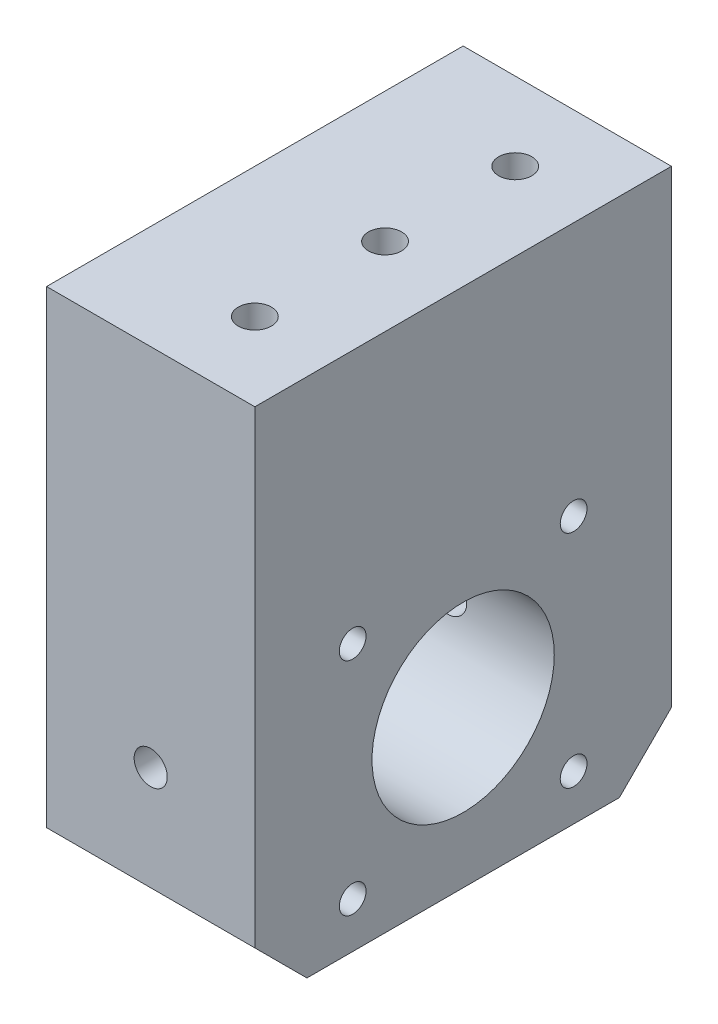
SolidWorks part; units mm, degrees
material "Nylon 6/10"
ref_plane "Front Plane" through (0, 0, 0) normal (0, 0, 1) x (1, 0, 0)
ref_plane "Top Plane" through (0, 0, 0) normal (0, 1, 0) x (1, 0, 0)
ref_plane "Right Plane" through (0, 0, 0) normal (1, 0, 0) x (0, 0, -1)
sketch "Sketch1" plane through (0, 0, 0) normal (1, 0, 0) x (0, 0, -1)
  line L1 (-25.4, -31.75) -> (25.4, -31.75)
  line L2 (-25.4, -31.75) -> (-25.4, 31.75)
  line L3 (-25.4, 31.75) -> (25.4, 31.75)
  line L4 (25.4, -31.75) -> (25.4, 31.75)
  line L5 (-25.4, -31.75) -> (25.4, 31.75) construction
  line L6 (-25.4, 31.75) -> (25.4, -31.75) construction
  point P0 (0, 0)
  dimension "D1" = 50.8
  dimension "D2" = 63.5
extrude "Base" add sketch "Sketch1" along normal blind 25.4
hole_wizard "7/8 (0.875) Diameter Hole1" positions "Sketch3" profile "Sketch2" hole size "7/8" standard "ANSI Inch" end condition through all
sketch "Sketch3" plane through (25.4, 0, 0) normal (1, 0, 0) x (0, 0, -1)
  line L1 (25.4, 31.75) -> (-25.4, 31.75) construction
  line L2 (0, -31.75) -> (0, 31.75) construction
  line L3 (-25.4, -31.75) -> (25.4, -31.75) construction
  point P0 (0, -12.7)
  dimension "D1" = 44.45
sketch "Sketch2" plane through (25.4, -12.7, 0) normal (0, 1, 0) x (0, 0, -1)
  line L0 (0, 0) -> (0, 25.4)
  line L1 (0, 25.4) -> (11.1125, 25.4)
  line L2 (11.1125, 25.4) -> (11.1125, 0)
  line L5 (11.1125, 0) -> (0, 0)
  line L11 (0, -6.35) -> (0, 107.95) construction
  dimension "Thru Hole Dia." = 22.225
  dimension "Thru Hole Depth" = 25.4
hole_wizard "#10-32 Tapped Hole1" positions "Sketch12" profile "Sketch11" tap size "#10-32" standard "ANSI Inch"
sketch "Sketch12" plane through (0, 31.75, 0) normal (0, 1, 0) x (1, 0, 0)
  line L0 (15.875, 25.4) -> (15.875, -25.4) construction
  line L1 (25.4, 25.4) -> (0, 25.4) construction
  line L2 (25.4, -25.4) -> (0, -25.4) construction
  line L3 (25.4, 0) -> (0, 0) construction
  line L4 (25.4, 25.4) -> (25.4, -25.4) construction
  line L5 (0, 25.4) -> (0, -25.4) construction
  point P0 (15.875, 15.875)
  point P2 (15.875, -15.875)
  point P13 (15.875, 0)
  dimension "D1" = 9.525
  dimension "D2" = 9.525
  dimension "D3" = 9.525
sketch "Sketch11" plane through (15.875, 31.75, -15.875) normal (1, 0, 0) x (0, 0, 1)
  line L0 (0, 0) -> (0, 26.6133)
  line L1 (0, 26.6133) -> (2.0193, 25.4)
  line L2 (2.0193, 25.4) -> (2.0193, 0)
  line L5 (2.0193, 0) -> (0, 0)
  line L10 (0, 26.6133) -> (-2.0193, 25.4) construction
  line L11 (0, -6.35) -> (0, 107.95) construction
  dimension "Tap Drill Dia." = 4.0386
  dimension "Tap Drill Depth" = 25.4
  dimension "Drill Angle" = 118
hole_wizard "CBORE for #4 Socket Head Cap Screw1" positions "Sketch14" profile "Sketch13" counterbore size "#4" standard "ANSI Inch" end condition through all
sketch "Sketch14" plane through (0, 0, 0) normal (-1, 0, 0) x (0, 0, 1)
  line L0 (0, 31.75) -> (0, -31.75) construction
  line L1 (-25.4, 31.75) -> (25.4, 31.75) construction
  line L2 (25.4, -31.75) -> (-25.4, -31.75) construction
  line L3 (0, -12.7) -> (-13.4704, 0.7704) construction
  circle A1 centre (0, -12.7) radius 11.1125 construction
  circle A2 centre (0, -12.7) radius 11.1125
  point P0 (-13.4704, 0.7704)
  dimension "D1" = 19.05
  dimension "D2" = 45
sketch "Sketch13" plane through (0, 0.7704, -13.4704) normal (0, 1, 0) x (0, 0, 1)
  line L0 (0, 0) -> (0, 25.4)
  line L1 (0, 25.4) -> (1.6319, 25.4)
  line L3 (1.6319, 25.4) -> (1.632, 2.8448)
  line L4 (1.632, 2.8448) -> (2.7788, 2.8448)
  line L5 (2.7788, 2.8448) -> (2.7788, 0)
  line L7 (2.7788, 0) -> (0, 0)
  line L11 (0, -6.35) -> (0, 107.95) construction
  dimension "Thru Hole Dia." = 3.2639
  dimension "Thru Hole Depth" = 25.4
  dimension "C'Bore Dia." = 5.5575
  dimension "C'Bore Depth" = 2.8448
pattern_circular "CirPattern1" count 4 over 360 about axis through (0, -12.7, 0) along (1, 0, 0) of "CBORE for #4 Socket Head Cap Screw1"
chamfer "Chamfer2" distance 6.35 angle 45 2 edges at (12.7, -31.75, 25.4) (12.7, -31.75, -25.4)
hole_wizard "#10-32 Tapped Hole2" positions "Sketch16" profile "Sketch15" tap size "#10-32" standard "ANSI Inch" end condition through all
sketch "Sketch16" plane through (0, 0, -25.4) normal (0, 0, -1) x (-1, 0, 0)
  line L0 (-25.4, -1.5875) -> (-25.4, -23.8125) construction
  line L1 (-25.4, -1.5875) -> (-25.4, -23.8125)
  line L4 (-25.4, -12.7) -> (0, -12.7) construction
  line L6 (0, -25.4) -> (0, 31.75) construction
  point P0 (-12.7, -12.7)
sketch "Sketch15" plane through (12.7, -12.7, -25.4) normal (1, 0, 0) x (0, 1, 0)
  line L0 (0, 0) -> (0, 50.8)
  line L1 (0, 50.8) -> (2.0193, 50.8)
  line L2 (2.0193, 50.8) -> (2.0193, 0)
  line L5 (2.0193, 0) -> (0, 0)
  line L11 (0, -6.35) -> (0, 107.95) construction
  dimension "Thru Tap Drill Dia." = 4.0386
  dimension "Thru Tap Drill Depth" = 50.8
cosmetic thread "Hole Thread1" parameters "D2"=4.826
